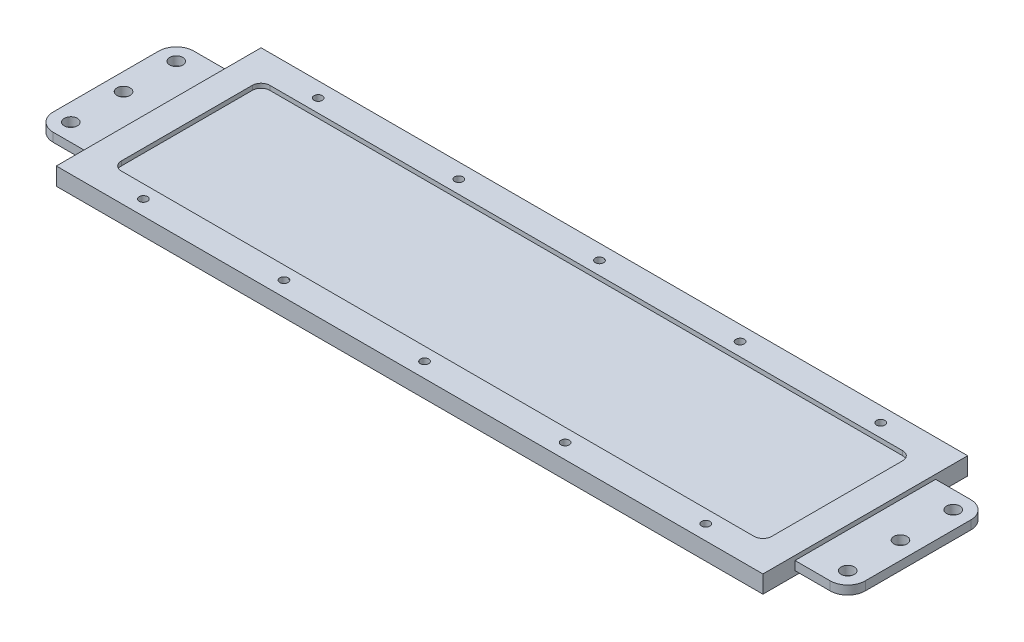
SolidWorks part; units mm, degrees
ref_plane "Front Plane" through (0, 0, 0) normal (0, 0, 1) x (1, 0, 0)
ref_plane "Top Plane" through (0, 0, 0) normal (0, 1, 0) x (1, 0, 0)
ref_plane "Right Plane" through (0, 0, 0) normal (1, 0, 0) x (0, 0, -1)
sketch "Sketch1" plane through (0, 0, 0) normal (0, 1, 0) x (1, 0, 0)
  line L0 (3.81, 3.81) -> (3.81, 70.1599) construction
  line L1 (0, 0) -> (255.27, 0)
  line L2 (0, 0) -> (0, 73.9699)
  line L3 (0, 73.9699) -> (255.27, 73.9699)
  line L4 (255.27, 0) -> (255.27, 73.9699)
  line L5 (6.985, 66.9849) -> (195.485, 66.9849) construction
  line L6 (6.985, 66.9849) -> (6.985, 6.985) construction
  line L7 (6.985, 6.985) -> (195.485, 6.985) construction
  line L8 (195.485, 66.9849) -> (195.485, 6.985) construction
  line L9 (3.81, 70.1599) -> (251.46, 70.1599) construction
  line L10 (251.46, 3.81) -> (251.46, 70.1599) construction
  line L11 (3.81, 3.81) -> (251.46, 3.81) construction
  line L12 (565.2908, 402.2635) -> (1930.6241, 402.2635) construction
  line L13 (-12.7, 56.0349) -> (-12.7, 17.9349) construction
  line L28 (127.635, 73.9699) -> (127.635, 0) construction
  line L29 (127.635, 70.1599) -> (127.635, 66.9849) construction
  line L30 (0, 36.9849) -> (255.27, 36.9849) construction
  line L31 (0, 62.3849) -> (-12.7, 62.3849)
  line L32 (0, 62.3849) -> (0, 11.5849)
  line L33 (0, 11.5849) -> (-12.7, 11.5849)
  line L34 (-19.05, 56.0349) -> (-19.05, 17.9349)
  line L35 (267.97, 56.0349) -> (267.97, 17.9349) construction
  line L36 (274.32, 56.0349) -> (274.32, 17.9349)
  line L37 (255.27, 11.5849) -> (267.97, 11.5849)
  line L38 (255.27, 62.3849) -> (255.27, 11.5849)
  line L39 (255.27, 62.3849) -> (267.97, 62.3849)
  circle A0 centre (178.435, 68.5724) radius 1.5
  circle A1 centre (178.435, 5.3975) radius 1.5
  circle A2 centre (229.235, 68.5724) radius 1.5
  circle A3 centre (229.235, 5.3975) radius 1.5
  circle A4 centre (214.6468, 59.9999) radius 3.81 construction
  circle A15 centre (127.635, 68.5724) radius 1.5
  circle A20 centre (127.635, 5.3975) radius 1.5
  circle A21 centre (26.035, 5.3975) radius 1.5
  circle A22 centre (76.835, 5.3975) radius 1.5
  circle A23 centre (26.035, 68.5724) radius 1.5
  circle A24 centre (76.835, 68.5724) radius 1.5
  circle A25 centre (-12.7, 56.0349) radius 2.3812
  circle A26 centre (-12.7, 17.9349) radius 2.3813
  arc A27 (-12.7, 62.3849) -> (-19.05, 56.0349) centre (-12.7, 56.0349) ccw
  arc A28 (-19.05, 17.9349) -> (-12.7, 11.5849) centre (-12.7, 17.9349) ccw
  arc A29 (274.32, 17.9349) -> (267.97, 11.5849) centre (267.97, 17.9349) cw
  arc A30 (267.97, 62.3849) -> (274.32, 56.0349) centre (267.97, 56.0349) cw
  circle A31 centre (267.97, 17.9349) radius 2.3813
  circle A32 centre (267.97, 56.0349) radius 2.3813
  circle A33 centre (-12.7, 36.9849) radius 2.3812
  circle A34 centre (267.97, 36.9849) radius 2.3813
  point P36 (-19.05, 36.9849)
  point P42 (-12.7, 36.9849)
  point P48 (127.635, 68.5724)
  dimension "D6" = 3.175
  dimension "D11" = 7.62
  dimension "D13" = 188.5
  dimension "D15" = 3
  dimension "D21" = 4.7625
  dimension "D19" = 6.35
  dimension "D24" = 6.35
  dimension "D1" = 59.9999
  dimension "D2" = 3.175
  dimension "D3" = 3.175
  dimension "D4" = 3.81
  dimension "D5" = 3.81
  dimension "D7" = 3.81
  dimension "D8" = 3.81
  dimension "D9" = 19.1618
  dimension "D10" = 10.16
  dimension "D12" = 73.9699
  dimension "D14" = 55.975
  dimension "D16" = 3
  dimension "D17" = 50.8
  dimension "D18" = 50.8
  dimension "D20" = 6.35
  dimension "D22" = 38.1
  dimension "D23" = 19.05
  dimension "D25" = 293.37
  dimension "D26" = 66.3499
extrude "Boss-Extrude1" add sketch "Sketch1" along normal blind 1.5875 and the other way blind 1.5875 contours A30 L39 L4 L37 A29 L36 A31 A32 | L34 A28 L33 L2 L31 A27 A25 A26 | L1 L4 L3 L2 A23 A22 A21 A3 A2 A0 A1 A15 A20 A24 region at (127.635, 0, -36.9849) region at (-9.1794, 0, -36.9849) region at (264.4494, 0, -36.9849)
extrude "Boss-Extrude2" add sketch "Sketch1<4>" along normal blind 3.175 and the other way blind 3.175 contours L1 L4 L3 L2
sketch "Sketch1<4>" plane through (0, 0, 0) normal (0, 1, 0) x (1, 0, 0) same geometry as "Sketch1"
sketch "Sketch2" plane through (0, 3.175, 0) normal (0, 1, 0) x (1, 0, 0)
  line L0 (6.985, 66.9849) -> (195.485, 66.9849) construction
  line L1 (13.335, 63.8099) -> (241.935, 63.8099)
  line L2 (10.16, 60.6349) -> (10.16, 13.335)
  line L3 (13.335, 10.16) -> (241.935, 10.16)
  line L4 (245.11, 60.6349) -> (245.11, 13.335)
  line L5 (6.985, 6.985) -> (195.485, 6.985) construction
  line L6 (6.985, 66.9849) -> (6.985, 6.985) construction
  line L7 (251.46, 3.81) -> (251.46, 70.1599) construction
  line L8 (0, 73.9699) -> (255.27, 73.9699) construction
  arc A0 (241.935, 63.8099) -> (245.11, 60.6349) centre (241.935, 60.6349) cw
  arc A1 (245.11, 13.335) -> (241.935, 10.16) centre (241.935, 13.335) cw
  arc A2 (13.335, 10.16) -> (10.16, 13.335) centre (13.335, 13.335) cw
  arc A3 (13.335, 63.8099) -> (10.16, 60.6349) centre (13.335, 60.6349) ccw
  dimension "D6" = 3.175
  dimension "D1" = 3.175
  dimension "D2" = 3.175
  dimension "D3" = 3.175
  dimension "D4" = 6.35
  dimension "D5" = 10.16
extrude "Cut-Extrude1" cut sketch "Sketch2" against normal blind 1.5875
mirror "Mirror1" about plane through (0, 0, 0) normal (0, 1, 0) of "Cut-Extrude1"
extrude "Cut-Extrude2" cut sketch "Sketch1<6>" against normal blind 3.175 and the other way blind 3.175 contours A2 | A3 | A1 | A0 | A15 | A24 | A22 | A20 | A21 | A23
sketch "Sketch1<6>" plane through (0, 0, 0) normal (0, 1, 0) x (1, 0, 0) same geometry as "Sketch1"
